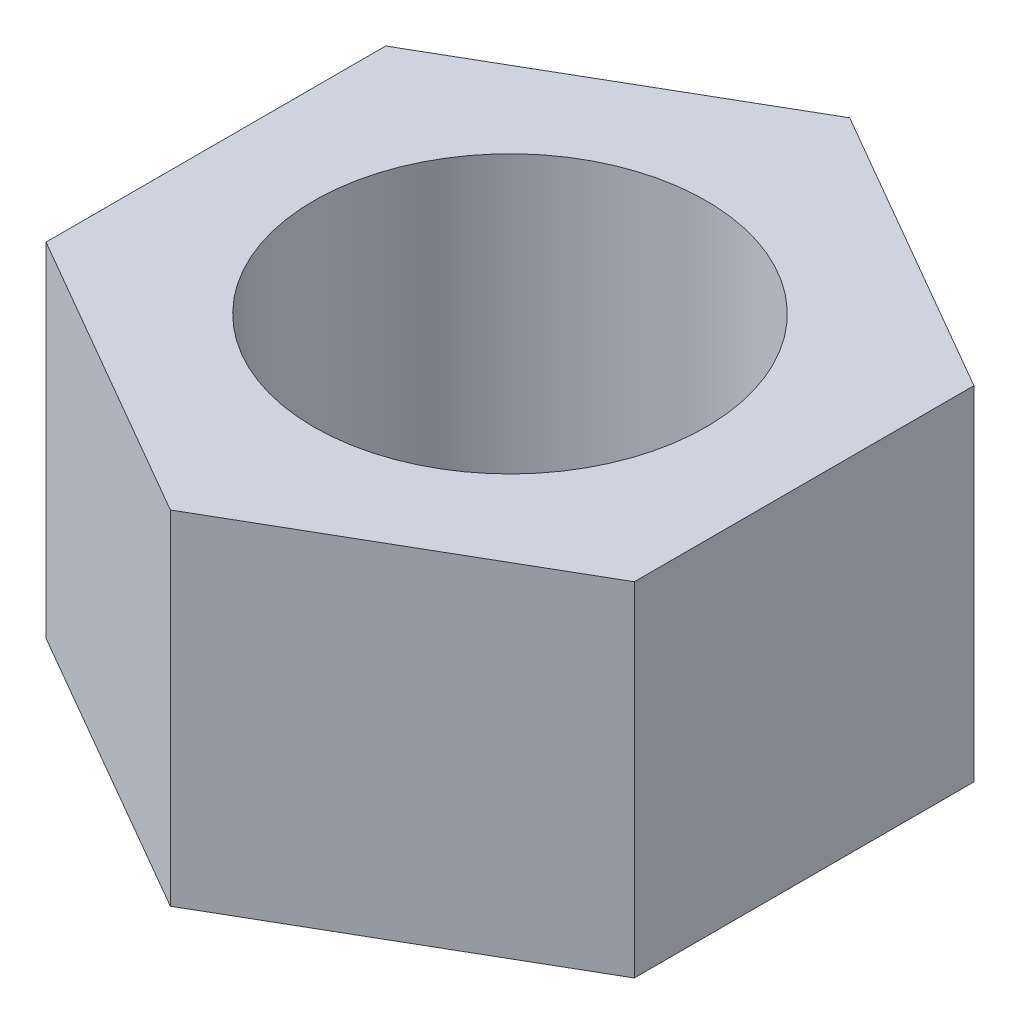
SolidWorks part; units mm, degrees
ref_plane "Front Plane" through (0, 0, 0) normal (0, 0, 1) x (1, 0, 0)
ref_plane "Top Plane" through (0, 0, 0) normal (0, 1, 0) x (1, 0, 0)
ref_plane "Right Plane" through (0, 0, 0) normal (1, 0, 0) x (0, 0, -1)
sketch "Sketch1" plane through (0, 0, 0) normal (0, 0, 1) x (1, 0, 0)
  line L0 (0, -4.1672) -> (0, 4.1672) construction
  line L1 (7.1438, 0) -> (-7.1438, 0) construction
  line L2 (4.7625, -4.1672) -> (-4.7625, -4.1672) construction
  line L3 (4.7625, -4.1672) -> (4.7625, -3.1089) construction
  point P4 (0, 0)
  point P8 (0, 0)
  point P11 (0, -4.1672)
  dimension "Height" = 8.3344
  dimension "Width" = 14.2875
  dimension "Thread Size" = 9.525
  dimension "Thread Pitch" = 1.0583
sketch "Sketch2" plane through (0, 0, 0) normal (1, 0, 0) x (0, 0, -1)
  line L0 (0, -4.1672) -> (0, 4.1672) construction
  line L1 (3.048, -1.9542) -> (-3.048, -1.9542)
  line L2 (3.048, -1.9542) -> (3.048, 4.1672)
  line L3 (3.048, 4.1672) -> (-3.048, 4.1672)
  line L4 (-3.048, -1.9542) -> (-3.048, 4.1672)
  line L5 (3.048, -1.9542) -> (-3.048, 4.1672) construction
  line L6 (3.048, 4.1672) -> (-3.048, -1.9542) construction
  point P0 (0, 1.1065)
  point P7 (0, 4.1672)
  dimension "Minimum Slot Width" = 6.096
  dimension "Minimum Slot Depth" = 6.1214
sketch "Sketch11" plane through (0, 0, 0) normal (0, 1, 0) x (1, 0, 0)
  line L1 (0, 8.2489) -> (-7.1438, 4.1244)
  line L2 (-7.1438, 4.1244) -> (-7.1438, -4.1244)
  line L3 (-7.1438, -4.1244) -> (0, -8.2489)
  line L4 (0, -8.2489) -> (7.1438, -4.1244)
  line L5 (7.1438, -4.1244) -> (7.1438, 4.1244)
  line L6 (7.1438, 4.1244) -> (0, 8.2489)
  circle A0 centre (0, 0) radius 7.1438 construction
  circle A1 centre (0, 0) radius 4.7625
  point P19 (0, -4.7625)
extrude "Boss-Extrude1" add sketch "Sketch11" along normal up to vertex (4.1672 mm away) and the other way up to vertex (4.1672 mm away) up to point (0, 4.1672, 0) other way up to point (0, -4.1672, 0)
fillet "Fillet1" [suppressed] radius 0.4286
sketch "Sketch3" plane through (0, 0, 0) normal (1, 0, 0) x (0, 0, -1)
  line L1 (4.1244, 4.1672) -> (8.2489, 4.1672) construction
  line L2 (6.4294, -4.1672) -> (8.2489, -3.1167)
  line L3 (4.1244, -4.1672) -> (8.2489, -4.1672) construction
  line L4 (8.2489, 4.1672) -> (8.2489, -4.1672) construction
  line L5 (8.2489, -3.1167) -> (8.2489, -4.1672)
  line L7 (6.7151, 4.1672) -> (8.2489, 3.2817)
  line L8 (8.2489, 3.2817) -> (8.2489, 4.1672)
  line L10 (6.4294, -4.1672) -> (8.2489, -4.1672)
  line L12 (6.7151, 0) -> (7.1438, 0) construction
  line L16 (6.7151, 4.1672) -> (8.2489, 4.1672)
  line L21 (4.7625, -4.1672) -> (4.7625, -3.9291)
  line L22 (-4.1244, -4.1672) -> (4.1244, -4.1672) construction
  line L24 (5.0006, -4.1672) -> (4.7625, -4.1672)
  line L25 (4.7625, -3.9291) -> (5.0006, -4.1672)
  line L26 (4.7625, 4.1672) -> (4.7625, 3.9291)
  line L27 (4.7625, 4.1672) -> (5.0006, 4.1672)
  line L28 (5.0006, 4.1672) -> (4.7625, 3.9291)
  line L29 (3.048, 4.1672) -> (-3.048, 4.1672) construction
  line L30 (5.0006, 0) -> (5.4293, 0) construction
  line L31 (6.2865, 0) -> (6.7151, 0) construction
  line L32 (5.4293, 0) -> (5.8579, 0) construction
  line L33 (5.8579, 0) -> (6.2865, 0) construction
  point P0 (6.7151, 4.1672)
  point P1 (7.1438, 0)
  point P14 (4.7625, 0)
  point P36 (7.1438, -4.1672)
  point P44 (6.9294, 0)
  dimension "D2" = 30
  dimension "D5" = 0.2381
  dimension "D7" = 0.7144
  dimension "D1" = 30
revolve "Cut-Revolve2" [suppressed] cut sketch "Sketch3" angle 360 about L0
sketch "Sketch15" [suppressed] plane through (15.4781, 0, 17.1852) normal (0.5, 0, -0.866) x (-0.866, 0, -0.5)
  line L0 (21.997, 3.9197) -> (21.997, 2.0011) construction
  line L1 (21.997, -1.8361) -> (21.997, 0.0825) construction
  line L2 (21.997, 0.0825) -> (21.997, 2.0011) construction
  line L3 (21.997, -1.8361) -> (21.997, -3.7547) construction
  line L6 (20.8893, 0.0825) -> (21.4432, -0.8768)
  line L7 (21.4432, -0.8768) -> (22.5509, -0.8768)
  line L8 (22.5509, -0.8768) -> (23.1048, 0.0825)
  line L9 (23.1048, 0.0825) -> (22.5509, 1.0418)
  line L10 (22.5509, 1.0418) -> (21.4432, 1.0418)
  line L11 (21.4432, 1.0418) -> (20.8893, 0.0825)
  circle A0 centre (21.997, 0.0825) radius 0.9593 construction
  spline S4 degree 3 poles (17.8726, 3.2817) (18.546, 3.4761) (19.2244, 3.6363) (20.5953, 3.8583) (21.2879, 3.9193) (22.3398, 3.9199) (22.6921, 3.905) (23.389, 3.8469) (23.7351, 3.8037) (24.7673, 3.6369) (25.4472, 3.4763) (26.1215, 3.2817) knots 0 0 0 0 0.25 0.25 0.5 0.5 0.625 0.625 0.75 0.75 1 1 1 1 construction
  spline S5 degree 3 poles (26.1215, -3.1167) (25.448, -3.3111) (24.7697, -3.4713) (23.3988, -3.6933) (22.7062, -3.7543) (21.6543, -3.755) (21.302, -3.74) (20.6051, -3.6819) (20.259, -3.6387) (19.2268, -3.472) (18.5469, -3.3113) (17.8726, -3.1167) knots 0 0 0 0 0.25 0.25 0.5 0.5 0.625 0.625 0.75 0.75 1 1 1 1 construction
  point P1 (21.997, 1.0418)
  point P6 (21.997, 0)
extrude "Cut-Extrude2" [suppressed] cut sketch "Sketch15" along normal blind 0.1905
sketch "Sketch18" [suppressed] plane through (0, 4.1672, 0) normal (0, 1, 0) x (1, 0, 0)
  line L0 (0, 0) -> (0, -6.7151) construction
  line L1 (0, 0) -> (-4.1421, -4.1421) construction
  line L2 (0, 0) -> (-1.5161, -5.6583) construction
  line L3 (-6.7151, 0) -> (-6.3722, 0) construction
  line L4 (-6.3722, 0) -> (-6.0293, 0) construction
  line L5 (-6.0293, 0) -> (-5.6864, 0) construction
  line L6 (-5.6864, 0) -> (-5.3435, 0) construction
  line L7 (-5.3435, 0) -> (-5.0006, 0) construction
  line L8 (0, 0) -> (-3.5719, -6.1867) construction
  line L9 (-7.1437, -4.1244) -> (0, -8.2489) construction
  circle A0 centre (0, 0) radius 6.7151 construction
  circle A1 centre (0, 0) radius 5.0006 construction
  arc A2 (-4.1421, -4.1421) -> (-1.5161, -5.6583) centre (0, 0) ccw construction
  arc A3 (-4.2634, -4.2634) -> (-1.5605, -5.8239) centre (0, 0) ccw
  arc A4 (-4.0209, -4.0209) -> (-1.4718, -5.4927) centre (0, 0) ccw
  arc A5 (-4.0209, -4.0209) -> (-4.2634, -4.2634) centre (-4.1421, -4.1421) ccw
  arc A6 (-1.5605, -5.8239) -> (-1.4718, -5.4927) centre (-1.5161, -5.6583) ccw
  arc A7 (4.1421, -4.1421) -> (1.5161, -5.6583) centre (0, 0) cw construction
  arc A8 (4.2634, -4.2634) -> (1.5605, -5.8239) centre (0, 0) cw
  arc A9 (4.0209, -4.0209) -> (1.4718, -5.4927) centre (0, 0) cw
  arc A10 (4.0209, -4.0209) -> (4.2634, -4.2634) centre (4.1421, -4.1421) cw
  arc A11 (1.5605, -5.8239) -> (1.4718, -5.4927) centre (1.5161, -5.6583) cw
  point P18 (-2.9289, -5.0731)
  point P30 (2.9289, -5.0731)
  dimension "D1" = 30
extrude "Cut-Extrude3" [suppressed] cut sketch "Sketch18" against normal blind 0.2381
sketch "Sketch5" [suppressed] plane through (0, 0, 0) normal (0, 1, 0) x (1, 0, 0)
  circle A1 centre (0, 0) radius 4.7625 construction
  point P0 (0, -4.7625)
sketch "Sketch6" [suppressed] plane through (0, 0, 0) normal (0, 0, 1) x (1, 0, 0)
  line L0 (4.7625, 4.1672) -> (4.7625, -4.1672)
  line L2 (0, -4.1672) -> (7.1438, -4.1672) construction
  line L3 (4.7625, -4.1672) -> (0, -4.1672)
  line L4 (0, -4.1672) -> (0, 4.1672)
  line L5 (0, -4.1672) -> (0, 4.1672) construction
  line L6 (0, 4.1672) -> (4.7625, 4.1672)
revolve "Revolve2" [suppressed] add sketch "Sketch6" angle 360 about L4
sketch "Sketch7" [suppressed] plane through (0, -4.1672, 0) normal (0, -1, 0) x (1, 0, 0)
  circle A2 centre (0, 0) radius 4.7625
  circle A3 centre (0, 0) radius 4.7625
  dimension "D1" = 0
curve "Helix/Spiral1" [suppressed] pitch 1.0583 height 8.3344 turns 7.875
sketch "Sketch8" [suppressed] plane through (0, 0, 0) normal (0, 0, 1) x (1, 0, 0)
  line L0 (4.8771, -4.101) -> (3.9605, -4.6302) construction
  line L1 (3.9605, -4.6302) -> (4.8771, -5.1594) construction
  line L2 (4.8771, -5.1594) -> (4.8771, -4.101) construction
  line L3 (4.0751, -4.5641) -> (4.0751, -4.6964)
  line L4 (4.7625, -4.1672) -> (4.7625, -5.0932) construction
  line L5 (4.7625, -4.6302) -> (4.8771, -4.6302) construction
  line L6 (3.9605, -4.6302) -> (4.0751, -4.6302) construction
  line L7 (4.8198, -4.6302) -> (4.8198, -5.1263) construction
  line L8 (4.0751, -4.5641) -> (4.8771, -4.101)
  line L9 (4.8771, -4.101) -> (4.8198, -5.1263)
  line L10 (4.0751, -4.6964) -> (4.8198, -5.1263)
  dimension "D1" = 1.0583
  dimension "D2" = 0.1323
sweep "Cut-Sweep1" [suppressed] cut profiles "Sketch8" path "Helix/Spiral1"
sketch "Sketch9" [suppressed] plane through (0, 0, 0) normal (0, 0, 1) x (1, 0, 0)
  line L0 (0, 0.5953) -> (0, -4.1672)
  line L1 (0, 0.5953) -> (0, 0.8334)
  line L2 (0, -4.1672) -> (4.7625, -4.1672)
  line L3 (4.7625, -4.1672) -> (5.0006, -4.1672)
  line L4 (5.0006, -4.1672) -> (0, 0.8334)
  dimension "D1" = 0.2381
revolve "Revolve3" [suppressed] add sketch "Sketch9" angle 360 about L0
sketch "Sketch14" [suppressed] plane through (0, 0, 0) normal (0, 0, 1) x (1, 0, 0)
  line L0 (5.0006, 4.1672) -> (0, 4.1672)
  line L1 (0, 4.1672) -> (0, -0.8334)
  line L2 (0, -0.8334) -> (5.0006, 4.1672)
revolve "Revolve4" [suppressed] add sketch "Sketch14" angle 360 about L1
sketch "Sketch10" [suppressed] plane through (0, -4.1672, 0) normal (0, -1, 0) x (1, 0, 0)
  circle A0 centre (0, 0) radius 5.0006 construction
  circle A1 centre (0, 0) radius 5.0006
extrude "Boss-Extrude2" [suppressed] add sketch "Sketch10" against normal up to surface (8.3344 mm away)
combine bodies "Combine1" [suppressed] operation type subtract main body 110 bodies to subtract 120
equation "\"D5@Sketch3\"=\"Thread Size@Sketch1\"*.025"
equation "\"D4@Helix/Spiral1\" = \"Thread Pitch@Sketch1\""
equation "\"D3@Helix/Spiral1\" = \"Height@Sketch1\""
equation "\"D1@Sketch8\" = \"Thread Pitch@Sketch1\""
equation "\"D2@Sketch8\" = \"Thread Pitch@Sketch1\" / 8"
equation "\"D1@Sketch9\"=\"Thread Size@Sketch1\" * .025"
equation "\"D1@Fillet1\"=\"Width@Sketch1\" * .03"
equation "\"D7@Sketch3\"=\"Width@Sketch1\"*.05"
equation "\"D1@Cut-Extrude2\" =  (  ( \"Width@Sketch1\" - \"Thread Size@Sketch1\" / 2 )  * .02 ) "
equation "\"D1@Cut-Extrude3\"=((\"width@sketch1\"-\"Thread Size@sketch1\"/2)*.025)"
